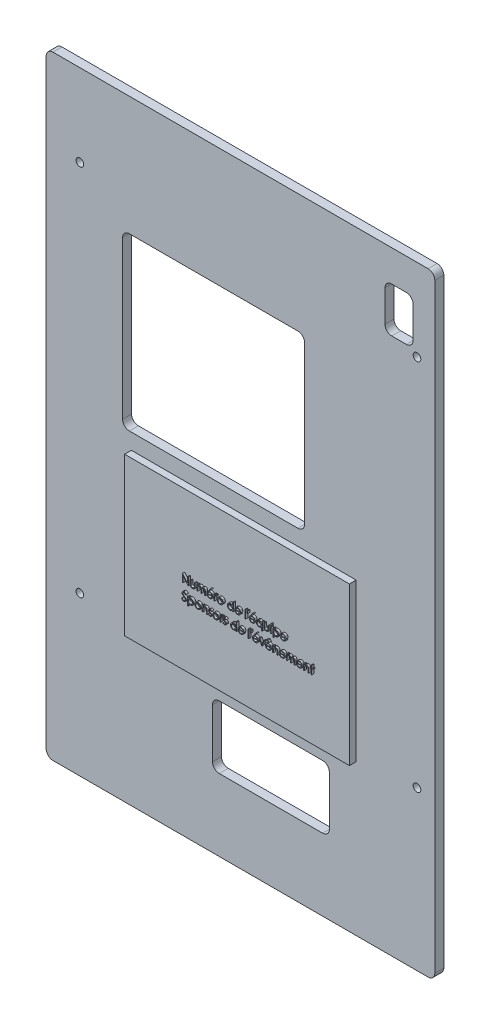
SolidWorks part; units mm, degrees
material "Verre"
ref_plane "Plan de face" through (0, 0, 0) normal (0, 0, 1) x (1, 0, 0)
ref_plane "Plan de dessus" through (0, 0, 0) normal (0, 1, 0) x (1, 0, 0)
ref_plane "Plan de droite" through (0, 0, 0) normal (1, 0, 0) x (0, 0, -1)
sketch "Esquisse1" plane through (0, 0, 0) normal (0, 0, 1) x (1, 0, 0)
  line L1 (0, 0) -> (172.93, 0)
  line L2 (0, 0) -> (0, 273)
  line L3 (0, 273) -> (172.93, 273)
  line L4 (172.93, 0) -> (172.93, 273)
  line L5 (74, 60) -> (126, 60)
  line L6 (74, 60) -> (74, 32)
  line L7 (74, 32) -> (126, 32)
  line L8 (126, 60) -> (126, 32)
  line L9 (34, 220) -> (115, 220)
  line L10 (34, 220) -> (34, 144)
  line L11 (34, 144) -> (115, 144)
  line L12 (115, 220) -> (115, 144)
  line L13 (163.25, 259) -> (150.75, 259)
  line L14 (163.25, 259) -> (163.25, 239)
  line L15 (163.25, 239) -> (150.75, 239)
  line L16 (150.75, 259) -> (150.75, 239)
  line L17 (163.25, 259) -> (150.75, 239) construction
  line L18 (163.25, 239) -> (150.75, 259) construction
  circle A0 centre (15, 236.5) radius 1.5
  circle A1 centre (165, 236.5) radius 1.5
  circle A2 centre (15, 70.5) radius 1.5
  circle A3 centre (165, 70.5) radius 1.5
  point P21 (157, 249)
  dimension "D5" = 3
  dimension "D8" = 3
  dimension "D11" = 3
  dimension "D22" = 3
  dimension "D25" = 12.5
  dimension "D1" = 172.93
  dimension "D2" = 273
  dimension "D3" = 36.5
  dimension "D4" = 15
  dimension "D6" = 7.93
  dimension "D7" = 36.5
  dimension "D9" = 70.5
  dimension "D10" = 15
  dimension "D12" = 74
  dimension "D13" = 52
  dimension "D14" = 28
  dimension "D15" = 32
  dimension "D16" = 34
  dimension "D17" = 81
  dimension "D18" = 144
  dimension "D19" = 76
  dimension "D20" = 7.93
  dimension "D21" = 70.5
  dimension "D23" = 15.93
  dimension "D24" = 24
  dimension "D26" = 20
extrude "Boss.-Extru.1" add sketch "Esquisse1" along normal blind 4
hole_wizard "Dégagement M31" positions "Esquisse2" profile "Esquisse3" hole size "M3" standard "ISO" end condition through all
sketch "Esquisse2" plane through (0, 0, 4) normal (0, 0, 1) x (1, 0, 0)
  point P0 (15, 236.5)
  point P3 (15, 70.5)
  point P6 (165, 236.5)
  point P9 (165, 70.5)
sketch "Esquisse3" plane through (15, 236.5, 4) normal (1, 0, 0) x (0, -1, 0)
  line L0 (0, 0) -> (0, 4)
  line L1 (0, 4) -> (1.7, 4)
  line L2 (1.7, 4) -> (1.7, 0)
  line L5 (1.7, 0) -> (0, 0)
  line L11 (0, -6.35) -> (0, 107.95) construction
  dimension "Diamètre du perçage jusqu'au prochain" = 3.4
  dimension "Profondeur du perçage jusqu'au prochain" = 4
fillet "Congé1" radius 3 16 edges at (0, 0, 2) (172.93, 0, 2) (126, 32, 2) (74, 32, 2) (126, 60, 2) (74, 60, 2) (115, 144, 2) (34, 144, 2) (115, 220, 2) (34, 220, 2) (172.93, 273, 2) (0, 273, 2) (163.25, 239, 2) (163.25, 259, 2) (150.75, 259, 2) (150.75, 239, 2)
sketch "Esquisse5" plane through (0, 0, 4) normal (0, 0, 1) x (1, 0, 0)
  line L0 (37, 144) -> (112, 144) construction
  line L1 (37.93, 137) -> (137.93, 137)
  line L2 (37.93, 137) -> (37.93, 67)
  line L3 (37.93, 67) -> (137.93, 67)
  line L4 (137.93, 137) -> (137.93, 67)
  line L5 (172.93, 3) -> (172.93, 270) construction
  line L6 (37.93, 102) -> (137.93, 102) construction
  dimension "D1" = 100
  dimension "D2" = 70
  dimension "D3" = 7
  dimension "D4" = 35
extrude "Boss.-Extru.3" add sketch "Esquisse5" along normal blind 3 contours L2 L3 L4 L1
sketch "Esquisse6" plane through (0, 0, 7) normal (0, 0, 1) x (1, 0, 0)
  text T0 "Numéro de l'équipe\r\nSponsors de l'évènement"
extrude "Boss.-Extru.4" add sketch "Esquisse6" along normal blind 1
